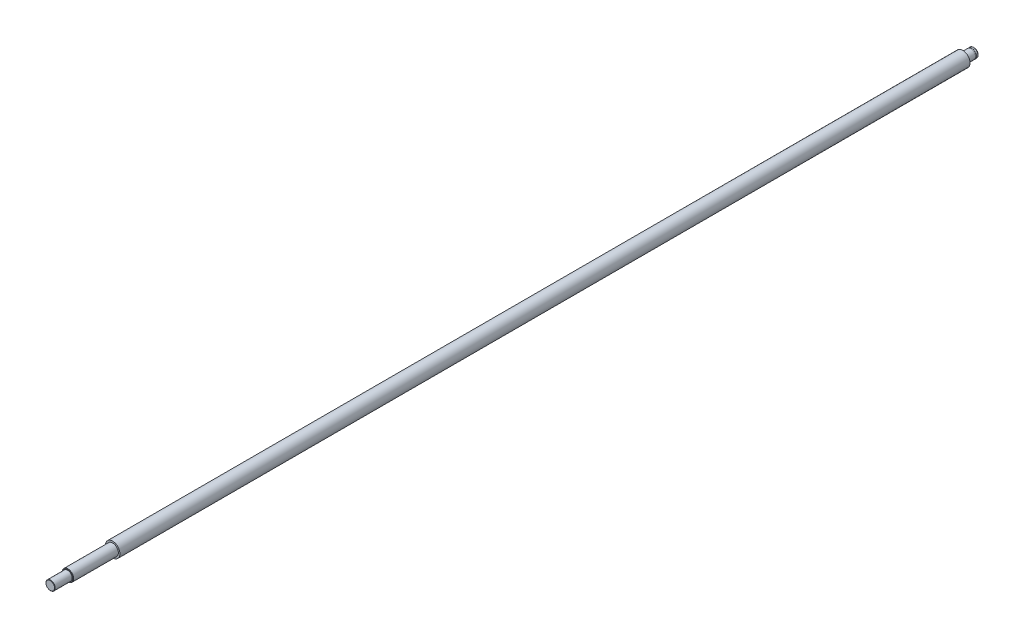
SolidWorks part; units mm, degrees
ref_plane "Front Plane" through (0, 0, 0) normal (0, 0, 1) x (1, 0, 0)
ref_plane "Top Plane" through (0, 0, 0) normal (0, 1, 0) x (1, 0, 0)
ref_plane "Right Plane" through (0, 0, 0) normal (1, 0, 0) x (0, 0, -1)
sketch "Sketch1" plane through (0, 0, 0) normal (1, 0, 0) x (0, 0, -1)
  line L0 (-400, 0) -> (400, 0)
  line L1 (-400, 0) -> (-400, 4)
  line L2 (-400, 4) -> (-385, 4)
  line L3 (-385, 4) -> (-385, 4.94)
  line L4 (-385, 4.94) -> (-346, 4.94)
  line L5 (-346, 4.94) -> (-346, 6.32)
  line L6 (-346, 6.32) -> (390, 6.32)
  line L7 (390, 6.32) -> (390, 4)
  line L8 (390, 4) -> (400, 4)
  line L9 (400, 4) -> (400, 0)
  dimension "D1" = 800
  dimension "D2" = 15
  dimension "D3" = 39
  dimension "D4" = 10
  dimension "D5" = 4
  dimension "D6" = 6.32
  dimension "D7" = 4.94
  dimension "D8" = 4
revolve "Revolve1" add sketch "Sketch1" angle 360 about L0
cosmetic thread "Cosmetic Thread1" parameters "D1"=5, "D2"=6.619
sketch "Sketch2" plane through (0, 0, 0) normal (1, 0, 0) x (0, 0, -1)
  line L0 (400, 4) -> (390, 4) construction
  line L1 (397.9, 4) -> (397, 4)
  line L2 (397.9, 4) -> (397.9, 3.8)
  line L3 (397.9, 3.8) -> (397, 3.8)
  line L4 (397, 4) -> (397, 3.8)
  line L5 (400, -4) -> (400, 4) construction
  line L6 (400, 0) -> (390, 0) construction
  line L7 (390, -6.32) -> (390, 6.32) construction
  dimension "D1" = 0.9
  dimension "D2" = 2.1
  dimension "D3" = 3.8
revolve "Cut-Revolve1" cut sketch "Sketch2" angle 360 about L6
chamfer "Chamfer1" distance 0.8 angle 45 1 edges at (4, 0, -400)
chamfer "Chamfer2" distance 0.3 angle 45 2 edges at (4, 0, 400) (4.94, 0, 385)
equation "\"length\"= 800mm"
equation "\"D1@Sketch1\"=\"length\""
